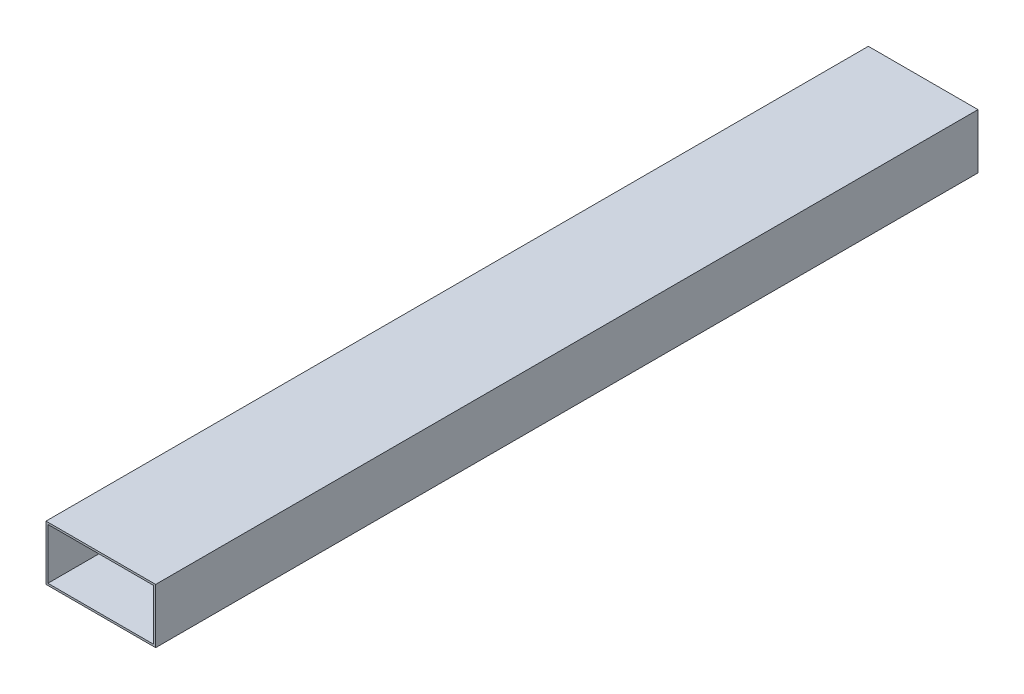
SolidWorks part; units mm, degrees
material "AISI 4130 Steel, annealed at 865C"
ref_plane "Front Plane" through (0, 0, 0) normal (0, 0, 1) x (1, 0, 0)
ref_plane "Top Plane" through (0, 0, 0) normal (0, 1, 0) x (1, 0, 0)
ref_plane "Right Plane" through (0, 0, 0) normal (1, 0, 0) x (0, 0, -1)
sketch "Sketch1" plane through (0, 0, 0) normal (0, 0, 1) x (1, 0, 0)
  line L0 (-24.511, -11.811) -> (-24.511, 11.811)
  line L1 (-25.4, -12.7) -> (25.4, -12.7)
  line L2 (-25.4, -12.7) -> (-25.4, 12.7)
  line L3 (-25.4, 12.7) -> (25.4, 12.7)
  line L4 (25.4, -12.7) -> (25.4, 12.7)
  line L5 (-25.4, -12.7) -> (25.4, 12.7) construction
  line L6 (-25.4, 12.7) -> (25.4, -12.7) construction
  line L7 (-24.511, 11.811) -> (24.511, 11.811)
  line L8 (24.511, -11.811) -> (24.511, 11.811)
  line L9 (-24.511, -11.811) -> (24.511, -11.811)
  point P0 (0, 0)
  dimension "D1" = 25.4
  dimension "D2" = 50.8
  dimension "D3" = 0.889
extrude "Boss-Extrude1" add sketch "Sketch1" along normal mid plane 381
ref_axis "Axis1" through (0, 0, -238.8791) along (0, 0, 1)
